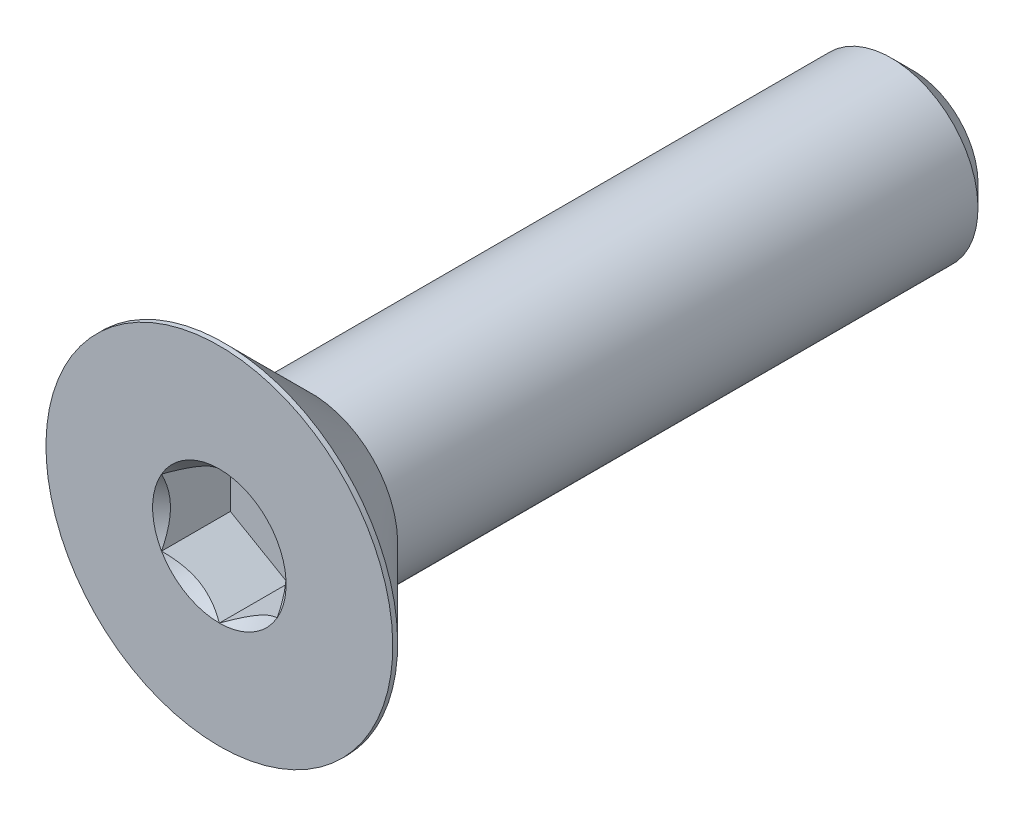
SolidWorks part; units mm, degrees
ref_plane "Front" through (0, 0, 0) normal (0, 0, 1) x (1, 0, 0)
ref_plane "Top" through (0, 0, 0) normal (0, 1, 0) x (1, 0, 0)
ref_plane "Right" through (0, 0, 0) normal (1, 0, 0) x (0, 0, -1)
sketch "Sketch11" plane through (0, 0, 0) normal (1, 0, 0) x (0, 0, -1)
  line L0 (-6, 3) -> (6, 3) construction
  line L5 (-6, 3) -> (-6, -3) construction
  line L6 (6, 1.5) -> (6, -1.5) construction
  line L7 (-5.99, 1) -> (-5.99, -1) construction
  line L8 (5.9688, 1.5541) -> (6.4688, 1.5541) construction
  line L9 (6.4688, 1.5541) -> (6.2188, 1.1211) construction
  line L10 (6.2188, 1.1211) -> (5.9688, 1.5541) construction
  line L11 (6.1875, 1.1752) -> (6.25, 1.1752) construction
  line L12 (6.2188, 1.1752) -> (6.2188, 1.1211) construction
  line L13 (5.9844, 1.5271) -> (6.4531, 1.5271) construction
  line L14 (6.2188, 1.5541) -> (6.2188, 1.5) construction
  line L15 (6, 1.5) -> (6.4375, 1.5) construction
  line L17 (-5.915, 3) -> (-2.915, 0) construction
  line L18 (-2.915, 0) -> (-5.915, -3) construction
  point P3 (-4.3, 3)
  point P8 (0, 3)
  point P21 (6.2188, 1.5271)
  point P26 (-6, 0)
  point P28 (-5.99, 0)
  point P29 (6, 0)
  dimension "Length" = 12
  dimension "Head Diameter" = 6
  dimension "Thread Major Diameter" = 3
  dimension "Head Height" = 1.7
  dimension "Drive Size" = 2
  dimension "Thread Pitch" = 0.5
  dimension "D1" = 0.0625
  dimension "D2" = 0.01
  dimension "D3" = 0.085
  dimension "Countersink Angle" = 90
sketch "Sketch1" plane through (0, 0, 0) normal (1, 0, 0) x (0, 0, -1)
  line L2 (-4.3, 1.5) -> (6, 1.5)
  line L3 (6, 1.5) -> (6, 0)
  line L4 (-4.81, 1.5) -> (-4.81, 0)
  line L5 (-4.3, 1.5) -> (-4.81, 1.5)
  line L6 (-6, 3) -> (-6, -3) construction
  line L7 (6, 1.5) -> (6, -1.5) construction
  line L8 (-4.81, 0) -> (6, 0)
  dimension "D1" = 1.19
revolve "Revolve1" add sketch "Sketch1" angle 360 mid plane about L8
chamfer "Chamfer1" distance 0.375 angle 45 1 edges at (0, -1.5, -6)
sketch "Sketch7" plane through (0, 0, 0) normal (1, 0, 0) x (0, 0, -1)
  line L2 (-6, 3) -> (-5.915, 3)
  line L5 (-4.3, 1.385) -> (-4.3, 0)
  line L6 (-6, 3) -> (-6, 0)
  line L8 (-6, 3) -> (-6, -3) construction
  line L9 (-6, 0) -> (-4.3, 0)
  line L12 (-5.915, 3) -> (-4.3, 1.385)
  line L13 (-5.915, 3) -> (-2.915, 0) construction
revolve "Revolve2" add sketch "Sketch7" angle 360 mid plane about L9 region at (0, 1.1696, 5.2571)
ref_plane "Plane1" through (0, 0, 4.3) normal (0, 0, 1) x (1, 0, 0)
sketch "Sketch5" plane through (0, 0, 6) normal (0, 0, 1) x (1, 0, 0)
  line L1 (1, -0.5774) -> (1, 0.5774)
  line L2 (1, 0.5774) -> (0, 1.1547)
  line L3 (0, 1.1547) -> (-1, 0.5774)
  line L4 (-1, 0.5774) -> (-1, -0.5774)
  line L5 (-1, -0.5774) -> (0, -1.1547)
  line L6 (0, -1.1547) -> (1, -0.5774)
  circle A0 centre (0, 0) radius 1 construction
extrude "Cut-Extrude2" cut sketch "Sketch5" against normal blind 1.19
sketch "Sketch6" plane through (0, 0, 6) normal (0, 0, -1) x (-1, 0, 0)
  circle A0 centre (0, 0) radius 1.1547
extrude "Cut-Extrude3" cut sketch "Sketch6" along normal blind 1.19 draft 45
sketch "Sketch12" plane through (0, 0, -6) normal (0, 0, -1) x (-1, 0, 0)
  circle A0 centre (0, 0) radius 1.5 construction
  circle A1 centre (0, 0) radius 1.5
curve "Helix/Spiral1" pitch 0.5 height 12 turns 24
sketch "Sketch13" plane through (0, 0, 0) normal (1, 0, 0) x (0, 0, -1)
  line L0 (5.9844, 1.5271) -> (6.4531, 1.5271)
  line L1 (6.4531, 1.5271) -> (6.25, 1.1752)
  line L2 (6.25, 1.1752) -> (6.1875, 1.1752)
  line L3 (6.1875, 1.1752) -> (5.9844, 1.5271)
sweep "Cut-Sweep1" [suppressed] cut profiles "Sketch13" path "Helix/Spiral1"
combine bodies "Combine1" operation type add bodies to combine 113 108
equation "\"D1@Chamfer1\"=\"Thread Pitch@Sketch11\" * .75"
equation "\"D1@Cut-Extrude2\"= \"Head Height@Sketch11\" * .7"
equation "\"D1@Cut-Extrude3\" = \"D1@Cut-Extrude2\""
equation "\"D1@Sketch11\"=\"Thread Pitch@Sketch11\"/8"
equation "\"D3@Sketch11\"=\"Head Height@Sketch11\"*.05"
equation "\"D4@Helix/Spiral1\"=\"Thread Pitch@Sketch11\""
equation "\"D1@Sketch1\"=\"Head Height@Sketch11\"*.7"
equation "\"D3@Helix/Spiral1\"=\"Length@Sketch11\""
